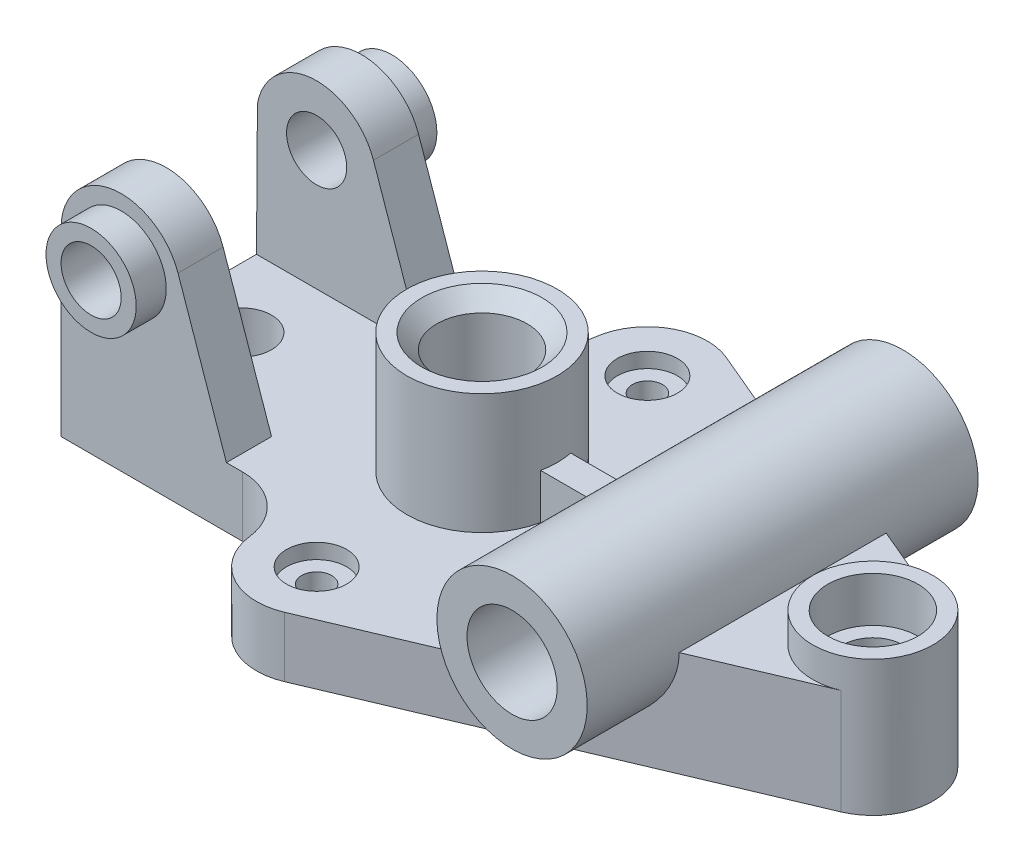
SolidWorks part; units mm, degrees
ref_plane "Front Plane" through (0, 0, 0) normal (0, 0, 1) x (1, 0, 0)
ref_plane "Top Plane" through (0, 0, 0) normal (0, 1, 0) x (1, 0, 0)
ref_plane "Right Plane" through (0, 0, 0) normal (1, 0, 0) x (0, 0, -1)
sketch "Sketch4" plane through (0, 0, 0) normal (0, 1, 0) x (1, 0, 0)
  line L0 (-77.2801, -56.6736) -> (-77.2801, 23.3264)
  line L1 (-77.2801, 23.3264) -> (-16.9664, 23.3264)
  line L2 (30.5127, 56.7457) -> (160.5127, 1.7457)
  line L3 (-77.2801, -16.6736) -> (152.7199, -16.6736) construction
  line L4 (30.5127, -90.0929) -> (160.5127, -35.0929)
  line L5 (-77.2801, -56.6736) -> (-16.9664, -56.6736)
  arc A0 (-16.9664, 23.3264) -> (2.8767, 40.8264) centre (-16.9664, 43.3264) ccw
  arc A1 (2.8767, 40.8264) -> (30.5127, 56.7457) centre (22.7199, 38.3264) cw
  arc A2 (160.5127, -35.0929) -> (160.5127, 1.7457) centre (152.7199, -16.6736) ccw
  circle A3 centre (-57.2801, -16.6736) radius 10
  arc A4 (2.8767, -74.1736) -> (30.5127, -90.0929) centre (22.7199, -71.6736) ccw
  arc A5 (-16.9664, -56.6736) -> (2.8767, -74.1736) centre (-16.9664, -76.6736) cw
  dimension "D2" = 20
  dimension "D5" = 20
  dimension "D6" = 20
  dimension "D7" = 80
  dimension "D8" = 40
  dimension "D1" = 40
  dimension "D3" = 210
  dimension "D4" = 20
  dimension "D9" = 55
extrude "Boss-Extrude1" add sketch "Sketch4" along normal blind 20
sketch "Sketch5" plane through (0, 0, 56.6736) normal (0, 0, 1) x (1, 0, 0)
  line L0 (-77.2801, 20) -> (-77.2801, 60)
  line L1 (-38.3791, 66.5384) -> (-22.2801, 20)
  line L2 (2.8767, 20) -> (-16.9664, 20) construction
  line L3 (-77.2801, 20) -> (-22.2801, 20)
  line L4 (-77.2801, 0) -> (-16.9664, 0) construction
  arc A0 (-77.2801, 60) -> (-38.3791, 66.5384) centre (-57.2801, 60) cw
  circle A1 centre (-57.2801, 60) radius 10
  dimension "D1" = 20
  dimension "D4" = 20
  dimension "D2" = 60
  dimension "D3" = 55
extrude "Boss-Extrude2" add sketch "Sketch5" against normal blind 15
sketch "Sketch6" plane through (0, 0, 56.6736) normal (0, 0, 1) x (1, 0, 0)
  circle A0 centre (-57.2801, 60) radius 15
  circle M8 centre (-57.2801, 60) radius 10
  dimension "D1" = 30
extrude "Boss-Extrude4" add sketch "Sketch6" along normal blind 10 contours M8 | A0 region at (-57.2801, 60, 56.6736)
sketch "Sketch10" plane through (0, 0, -23.3264) normal (0, 0, -1) x (-1, 0, 0)
  line L0 (22.2801, 20) -> (38.3791, 66.5384)
  line L1 (76.969, 63.514) -> (77.2801, 20)
  line L2 (77.2801, 20) -> (22.2801, 20)
  arc A0 (38.3791, 66.5384) -> (76.969, 63.514) centre (57.2801, 60) cw
  arc A1 (77.2801, 60) -> (38.3791, 66.5384) centre (57.2801, 60) ccw construction
  circle A2 centre (57.2801, 60) radius 10
  dimension "D1" = 20
extrude "Boss-Extrude6" add sketch "Sketch10" against normal blind 15
sketch "Sketch11" plane through (0, 0, -23.3264) normal (0, 0, -1) x (-1, 0, 0)
  circle A0 centre (57.2801, 60) radius 15
  circle M8 centre (57.2801, 60) radius 10
  dimension "D1" = 30
extrude "Boss-Extrude7" add sketch "Sketch11" along normal blind 10 contours A0 M8 region at (-42.7044, 60, -23.3264)
sketch "Sketch12" plane through (0, 20, 0) normal (0, 1, 0) x (1, 0, 0)
  line L0 (-77.2801, -16.6736) -> (172.7199, -16.6736) construction
  line L1 (-77.2801, 8.3264) -> (-77.2801, -41.6736) construction
  arc A0 (160.5127, -35.0929) -> (160.5127, 1.7457) centre (152.7199, -16.6736) ccw construction
  circle A1 centre (22.7199, -16.6736) radius 25
  circle A2 centre (-57.2801, -16.6736) radius 10 construction
  dimension "D1" = 80
  dimension "D2" = 50
extrude "Boss-Extrude8" add sketch "Sketch12" along normal blind 40 and the other way blind 35
hole_wizard "CSK for M10 Countersunk Flat Head Screw1" positions "3DSketch3" profile "Sketch18" countersink size "M10" standard "ISO" end condition through all
sketch3d "3DSketch3"
  line L0 (22.7199, 20, 16.6736) -> (22.7199, 60, 16.6736) construction
  point P0 (22.7199, 60, 16.6736)
sketch "Sketch18" plane through (22.7199, 60, 16.6736) normal (1, 0, 0) x (0, 0, 1)
  line L0 (0, 0) -> (0, 75)
  line L1 (0, 75) -> (20, 75)
  line L2 (15, 70) -> (15, 5)
  line L3 (15, 5) -> (20, 0)
  line L5 (20, 0) -> (0, 0)
  line L6 (-15, 5) -> (-20, 0) construction
  line L7 (20, 75) -> (15, 70)
  line L8 (-20, 75) -> (-15, 70) construction
  line L11 (0, -6.35) -> (0, 107.95) construction
  dimension "Thru Hole Dia." = 30
  dimension "Thru Hole Depth" = 75
  dimension "Near C'Sink Dia." = 40
  dimension "Near C'Sink Angle" = 90
  dimension "Far C'Sink Dia." = 40
  dimension "Far C'Sink Angle" = 90
sketch "Sketch19" plane through (0, 20, 0) normal (0, 1, 0) x (1, 0, 0)
  circle A0 centre (152.7199, -16.6736) radius 20
extrude "Boss-Extrude9" add sketch "Sketch19" along normal blind 25
hole_wizard "CBORE for M10 Hex Head Bolt3" positions "3DSketch4" profile "Sketch20" counterbore size "M10" standard "ISO" end condition through all
sketch3d "3DSketch4"
  line L0 (152.7199, 20, 16.6736) -> (152.7199, 0, 16.6736) construction
  point P0 (152.7199, 45, 16.6736)
sketch "Sketch20" plane through (152.7199, 45, 16.6736) normal (1, 0, 0) x (0, 0, 1)
  line L0 (0, 0) -> (0, 45)
  line L1 (10, 35) -> (20, 45)
  line L2 (10, 35) -> (10, 15)
  line L3 (10, 15) -> (15, 15)
  line L4 (15, 15) -> (15, 0)
  line L5 (15, 0) -> (0, 0)
  line L11 (0, -6.35) -> (0, 107.95) construction
  line L12 (20, 45) -> (0, 45)
  line L13 (-10, 35) -> (-20, 45) construction
  dimension "Thru Hole Dia." = 20
  dimension "Thru Hole Depth" = 45
  dimension "C'Bore Dia." = 30
  dimension "C'Bore Depth" = 15
  dimension "Far C'Sink Dia." = 40
  dimension "Far C'Sink Angle" = 90
sketch "Sketch23" plane through (0, 20, 0) normal (0, 1, 0) x (1, 0, 0)
  line L0 (160.5127, 1.7457) -> (72.7199, 38.8889)
  line L1 (160.5127, 1.7457) -> (30.5127, 56.7457) construction
  line L2 (72.7199, 38.8889) -> (72.7199, -72.2361)
  line L3 (30.5127, -90.0929) -> (160.5127, -35.0929) construction
  line L4 (72.7199, -72.2361) -> (160.5127, -35.0929)
  arc A0 (160.5127, -35.0929) -> (160.5127, 1.7457) centre (152.7199, -16.6736) ccw
  line M8 (30.5127, -90.0929) -> (160.5127, -35.0929)
  arc M9 (160.5127, -35.0929) -> (160.5127, 1.7457) centre (152.7199, -16.6736) cw
  line M10 (160.5127, 1.7457) -> (30.5127, 56.7457)
  dimension "D1" = 80
extrude "Boss-Extrude10" add sketch "Sketch23" along normal blind 15 contours L2 M10 M8 M9 region at (102.7401, 20, 16.6736)
ref_plane "Plane1" through (0, 0, 16.6736) normal (0, 0, -1) x (-1, 0, 0)
sketch "Sketch28" plane through (0, 0, 16.6736) normal (0, 0, -1) x (-1, 0, 0)
  line L0 (-160.5127, 35) -> (-72.7199, 35) construction
  line L1 (-160.5127, 0) -> (-30.5127, 0) construction
  line L3 (-132.7199, 45) -> (-172.7199, 45) construction
  line L4 (-153.5119, 45) -> (-153.5119, -26.6885) construction
  circle A0 centre (-97.7199, 35) radius 25
  dimension "D1" = 50
  dimension "D2" = 35
  dimension "D3" = 25
extrude "Boss-Extrude14" add sketch "Sketch28" along normal blind 65 and the other way blind 65
sketch "Sketch29" plane through (0, 0, -48.3264) normal (0, 0, -1) x (-1, 0, 0)
  circle A0 centre (-97.7199, 35) radius 15
  dimension "D1" = 30
extrude "Cut-Extrude2" cut sketch "Sketch29" against normal blind 181
sketch "Sketch31" plane through (0, 0, 16.6736) normal (0, 0, -1) x (-1, 0, 0)
  line L0 (-72.7199, 35) -> (-47.7199, 35)
  line L1 (-47.7199, 60) -> (-47.7199, 20) construction
rib "Rib3" sketch "Sketch31" sketch "Sketch31" thickness 10 extrusion direction parallel to sketch draft on no parameters "D1"=10
sketch "Sketch34" plane through (0, 20, 0) normal (0, 1, 0) x (1, 0, 0)
  circle A0 centre (22.7199, 38.3264) radius 5
  dimension "D1" = 10
extrude "Cut-Extrude3" cut sketch "Sketch34" against normal blind 31
sketch "Sketch35" plane through (0, 20, 0) normal (0, 1, 0) x (1, 0, 0)
  circle A0 centre (22.7199, 38.3264) radius 10
  dimension "D1" = 20
extrude "Cut-Extrude4" cut sketch "Sketch35" against normal blind 5
mirror "Mirror3" about plane through (0, 0, 16.6736) normal (0, 0, -1) of "Cut-Extrude3", "Cut-Extrude4"
